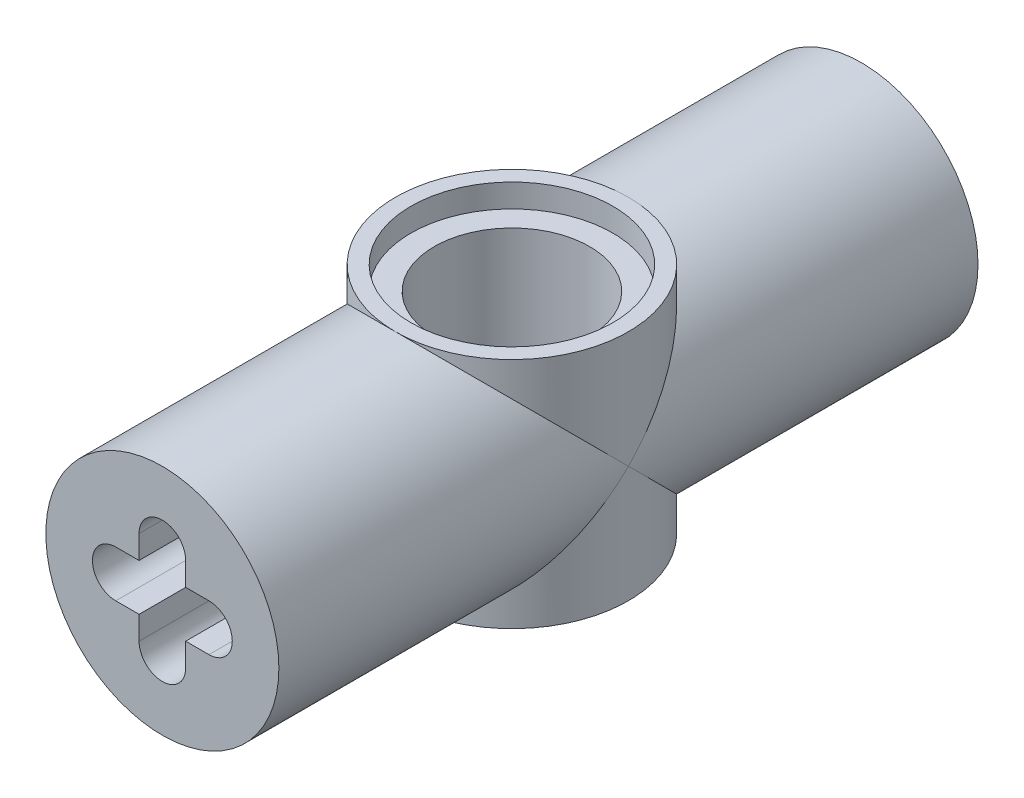
SolidWorks part; units mm, degrees
material "PVC Rigid"
ref_plane "Front Plane" through (0, 0, 0) normal (0, 0, 1) x (1, 0, 0)
ref_plane "Top Plane" through (0, 0, 0) normal (0, 1, 0) x (1, 0, 0)
ref_plane "Right Plane" through (0, 0, 0) normal (1, 0, 0) x (0, 0, -1)
sketch "Sketch1" plane through (0, 0, 0) normal (0, 0, 1) x (1, 0, 0)
  line L0 (0, 0) -> (3.048, 0) construction
  line L1 (0, 0.762) -> (3.048, 0.762)
  line L2 (0, -0.762) -> (3.048, -0.762)
  line L8 (1.524, 1.524) -> (1.524, -1.524) construction
  line L9 (2.286, 1.524) -> (2.286, -1.524)
  line L10 (0.762, 1.524) -> (0.762, -1.524)
  arc A0 (0, 0.762) -> (0, -0.762) centre (0, 0) ccw
  arc A2 (3.048, -0.762) -> (3.048, 0.762) centre (3.048, 0) ccw
  arc A4 (2.286, 1.524) -> (0.762, 1.524) centre (1.524, 1.524) ccw
  arc A5 (0.762, -1.524) -> (2.286, -1.524) centre (1.524, -1.524) ccw
  circle A7 centre (1.524, 0) radius 2.286 construction
  circle A8 centre (1.524, 0) radius 3.81
  point P1 (3.81, 0)
  point P3 (1.524, 0)
  point P8 (1.524, 0)
  point P13 (5.334, 0)
  point P15 (7.62, 0)
  point P17 (0, 3.302)
  point P18 (19.05, 3.302)
  point P19 (0, -3.302)
  point P20 (19.05, -3.302)
  point P23 (13.843, 0)
  point P24 (3.81, 0)
  point P25 (23.368, 0)
  point P26 (3.429, 0)
  point P27 (-7.874, -3.302)
  point P28 (7.874, -3.302)
  point P29 (-7.874, 3.302)
  point P30 (7.874, 3.302)
  point P35 (11.811, 0)
  point P60 (11.5175, 1.1139)
  dimension "D2" = 1.524
  dimension "D3" = 4.572
  dimension "D4" = 7.62
  dimension "D1" = 1.524
extrude "Boss-Extrude1" add sketch "Sketch1" along normal blind 22.86 contours A8 A5 L10 L2 A0 L1 A4 L9 A2 region at (-2.1782, 0, 0)
sketch "Sketch2" plane through (0, 0, 0) normal (0, 1, 0) x (1, 0, 0)
  line L0 (1.524, -1011.43) -> (1.524, 48988.57) construction
  circle A0 centre (1.524, -11.43) radius 3.81
  dimension "D1" = 11.43
extrude "Boss-Extrude2" add sketch "Sketch2" along normal blind 3.81 and the other way blind 3.81
sketch "Sketch4" plane through (0, 3.81, 0) normal (0, 1, 0) x (-1, 0, 0)
  circle A0 centre (-1.524, 11.43) radius 2.54
extrude "Cut-Extrude1" cut sketch "Sketch4" against normal through all
sketch "Sketch5" plane through (0, 3.81, 0) normal (0, 1, 0) x (1, 0, 0)
  circle A0 centre (1.524, -11.43) radius 3.302
extrude "Cut-Extrude2" cut sketch "Sketch5" against normal blind 0.762
sketch "Sketch6" plane through (0, -3.81, 0) normal (0, -1, 0) x (1, 0, 0)
  circle A0 centre (1.524, 11.43) radius 3.302
extrude "Cut-Extrude3" cut sketch "Sketch6" against normal blind 0.762
equation "\"D1@Sketch2\"=\"D1@Boss-Extrude1\"/2"
